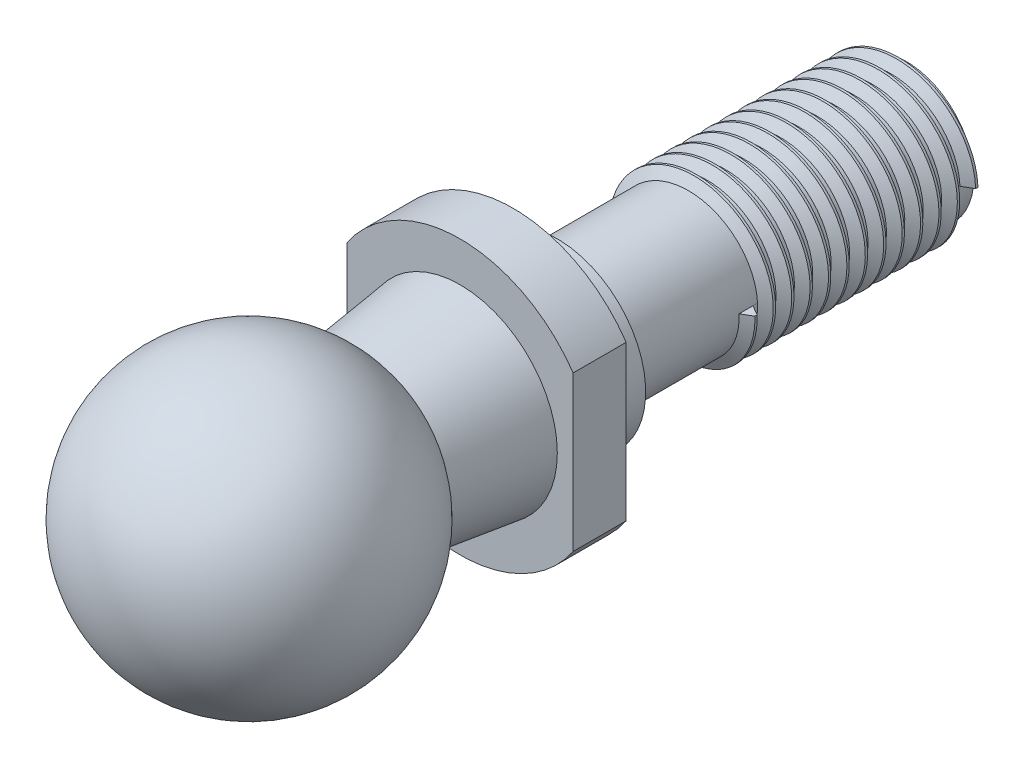
SolidWorks part; units mm, degrees
ref_plane "Front Plane" through (0, 0, 0) normal (0, 0, 1) x (1, 0, 0)
ref_plane "Top Plane" through (0, 0, 0) normal (0, 1, 0) x (1, 0, 0)
ref_plane "Right Plane" through (0, 0, 0) normal (1, 0, 0) x (0, 0, -1)
sketch "Sketch1" plane through (0, 0, 0) normal (1, 0, 0) x (0, 0, -1)
  line L0 (0, 8.255) -> (0, -8.255)
  arc A0 (0, 8.255) -> (0, -8.255) centre (0, 0) ccw
  dimension "D1" = 16.51
revolve "Revolve1" add sketch "Sketch1" angle 360 about L0
sketch "Sketch2" plane through (0, 0, 0) normal (1, 0, 0) x (0, 0, -1)
  line L0 (6.6564, 4.8824) -> (6.6564, 0)
  line L1 (6.6564, 0) -> (12.1382, 0)
  line L2 (12.1382, 0) -> (12.1382, 5.588)
  line L3 (12.1382, 5.588) -> (6.6564, 4.8824)
  circle A0 centre (0, 0) radius 8.255 construction
  dimension "D1" = 4.8824
  dimension "D2" = 5.588
  dimension "D3" = 5.4818
revolve "Revolve3" add sketch "Sketch2" angle 360 about L1
sketch "Sketch3" plane through (0, 0, -12.1382) normal (0, 0, -1) x (-1, 0, 0)
  line L0 (-6.4994, 4.445) -> (-6.4994, -4.445)
  line L1 (6.4994, 4.445) -> (6.4994, -4.445)
  arc A0 (-6.4994, -4.445) -> (6.4994, -4.445) centre (0, 0) ccw
  arc A1 (6.4994, 4.445) -> (-6.4994, 4.445) centre (0, 0) ccw
  dimension "D1" = 15.748
  dimension "D2" = 8.89
  dimension "D3" = 8.89
extrude "Boss-Extrude1" add sketch "Sketch3" along normal blind 3.048
sketch "Sketch4" plane through (0, 0, -15.1862) normal (0, 0, -1) x (-1, 0, 0)
  circle A0 centre (0, 0) radius 5.08
  dimension "D1" = 10.16
extrude "Boss-Extrude2" add sketch "Sketch4" along normal blind 2.54
sketch "Sketch5" plane through (0, 0, -17.7262) normal (0, 0, -1) x (-1, 0, 0)
  circle A0 centre (0, 0) radius 3.8796
  dimension "D1" = 7.7591
extrude "Boss-Extrude3" add sketch "Sketch5" along normal blind 20.066
thread "Thread1" pitch 1.0583 method extrude profile "Thread Profile1" start angle 0, offset 0, length 12.7, pitch 1.0583, diameter 7.7591
ref_plane "Plane1" through (3.8796, 0, -37.7922) normal (0, -1, 0) x (1, 0, 0)
sketch "Thread Profile1" plane through (3.8796, 0, -37.7922) normal (0, -1, 0) x (1, 0, 0)
  line L0 (0, 0) -> (0, 1.0583) construction
  line L1 (0, 0) -> (0.5728, 0.3307)
  line L2 (0.5728, 0.3307) -> (0.5728, 0.463)
  line L3 (0.5728, 0.463) -> (0, 0.7937)
  line L4 (0.5728, 0.3969) -> (0, 0.3969) construction
  line L11 (0, 0) -> (0, 0.7937)
  point P2 (0, 0)
  dimension "Pitch" = 1.0583
  dimension "Profile_Angle" = 60
  dimension "Profile_Land" = 0.1323
  dimension "Profile_Height" = 0.5728
